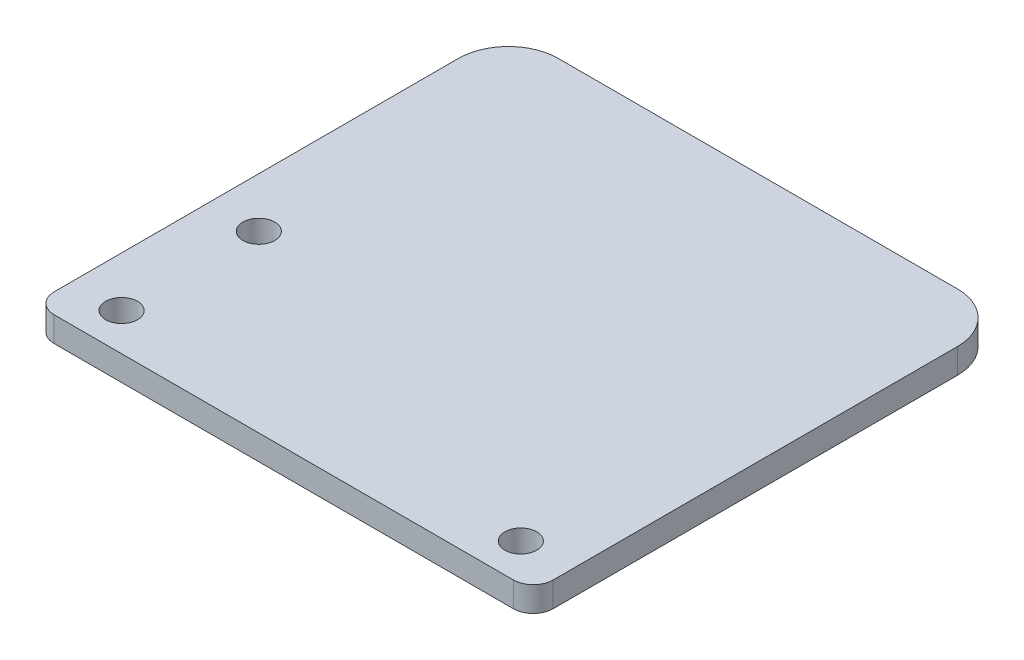
SolidWorks part; units mm, degrees
ref_plane "Front Plane" through (0, 0, 0) normal (0, 0, 1) x (1, 0, 0)
ref_plane "Top Plane" through (0, 0, 0) normal (0, 1, 0) x (1, 0, 0)
ref_plane "Right Plane" through (0, 0, 0) normal (1, 0, 0) x (0, 0, -1)
sketch "Sketch1" plane through (0, 0, 0) normal (0, 1, 0) x (1, 0, 0)
  line L1 (-31.75, 30.1625) -> (31.75, 30.1625)
  line L2 (-31.75, 30.1625) -> (-31.75, -30.1625)
  line L3 (-31.75, -30.1625) -> (31.75, -30.1625)
  line L4 (31.75, 30.1625) -> (31.75, -30.1625)
  line L5 (-31.75, 30.1625) -> (31.75, -30.1625) construction
  line L6 (-31.75, -30.1625) -> (31.75, 30.1625) construction
  point P0 (0, 0)
  dimension "D1" = 63.5
  dimension "D2" = 60.325
extrude "Boss-Extrude1" add sketch "Sketch1" along normal blind 3.175
sketch "Sketch2" plane through (0, 0, 0) normal (0, -1, 0) x (-1, 0, 0)
  line L0 (31.75, -30.1625) -> (-31.75, -30.1625) construction
  line L1 (-25.4, -25.4) -> (-31.75, -25.4) construction
  line L2 (-31.75, -30.1625) -> (-31.75, 30.1625) construction
  line L3 (25.4, -25.4) -> (31.75, -25.4) construction
  line L4 (31.75, 30.1625) -> (31.75, -30.1625) construction
  circle A0 centre (-25.4, -25.4) radius 2.032
  circle A1 centre (25.4, -25.4) radius 2.032
  dimension "D2" = 4.064
  dimension "D1" = 4.7625
  dimension "D3" = 50.8
extrude "Cut-Extrude1" cut sketch "Sketch2" against normal through all
fillet "Fillet1" radius 2.54 2 edges at (-31.75, 1.5875, 30.1625) (31.75, 1.5875, 30.1625)
fillet "Fillet2" radius 6.35 2 edges at (31.75, 1.5875, -30.1625) (-31.75, 1.5875, -30.1625)
sketch "Sketch3" plane through (0, 0, 0) normal (0, -1, 0) x (-1, 0, 0)
  line L0 (31.75, 23.8125) -> (31.75, -27.6225) construction
  line L1 (29.21, -30.1625) -> (-29.21, -30.1625) construction
  circle A0 centre (25.4, -7.9375) radius 2.032
  dimension "D1" = 4.064
  dimension "D2" = 6.35
  dimension "D3" = 22.225
extrude "Cut-Extrude2" cut sketch "Sketch3" against normal through all
